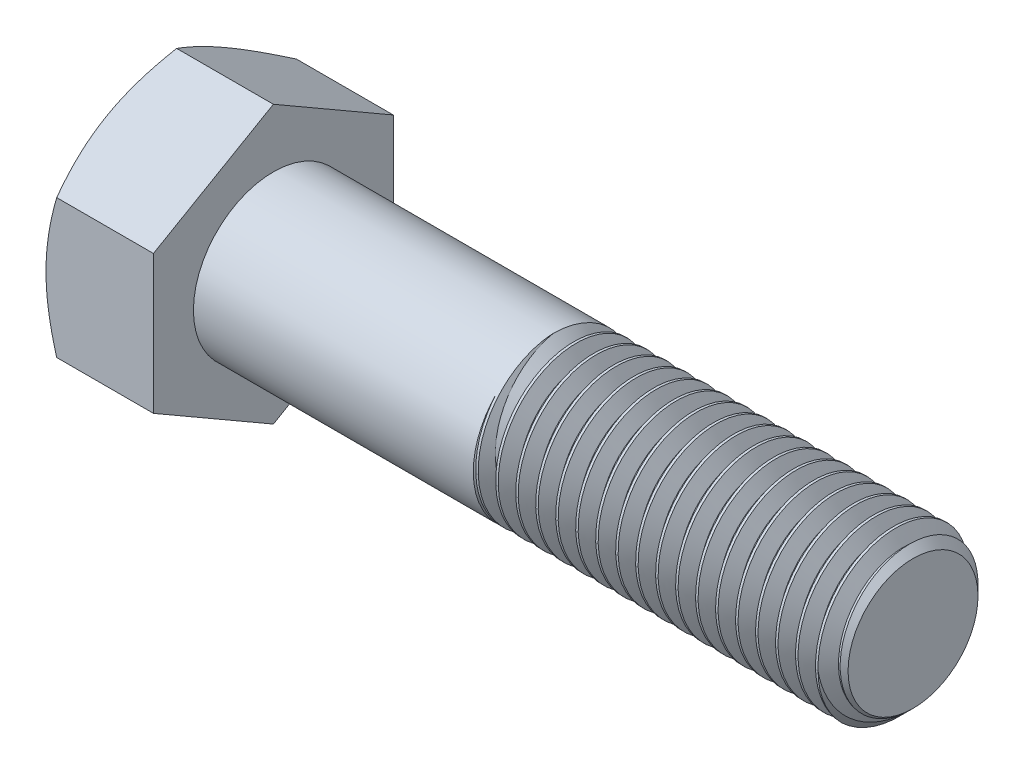
SolidWorks part; units mm, degrees
material "Alloy Steel"
ref_plane "Front Plane" through (0, 0, 0) normal (0, 0, 1) x (1, 0, 0)
ref_plane "Top Plane" through (0, 0, 0) normal (0, 1, 0) x (1, 0, 0)
ref_plane "Right Plane" through (0, 0, 0) normal (1, 0, 0) x (0, 0, -1)
sketch "Sketch1" plane through (0, 0, 0) normal (0, 0, 1) x (1, 0, 0)
  line L0 (-59.3328, 0) -> (59.3328, 0) construction
  line L1 (59.3328, 12.7) -> (59.3328, -12.7) construction
  line L2 (-42.2672, 19.05) -> (-42.2672, -19.05) construction
  line L3 (-59.3328, 19.05) -> (-59.3328, -19.05) construction
  point P9 (-42.2672, 0)
  point P10 (48.2203, -12.7)
  dimension "Screw Dia" = 25.4
  dimension "Hex" = 38.1
  dimension "Head Ht" = 17.0656
  dimension "Screw Lenght" = 101.6
  dimension "D1" = 11.1125
ref_plane "Plane2" through (59.3328, 0, 0) normal (1, 0, 0) x (0, 0, -1)
sketch "Sketch5" plane through (59.3328, 0, 0) normal (1, 0, 0) x (0, 0, -1)
  circle A0 centre (0, 0) radius 12.7
extrude "Boss-Extrude3" add sketch "Sketch5" against normal up to vertex (101.6 mm away) up to point (-42.2672, 0, 0)
sketch "Sketch9" plane through (59.3328, 0, 0) normal (1, 0, 0) x (0, 0, -1)
  circle A1 centre (0, 0) radius 12.7
  circle A2 centre (0, 0) radius 12.7
  dimension "D1" = 0
curve "Helix/Spiral1" pitch 3.175 height 60.325 turns 19 parameters "Pitch"=3.175
chamfer "Chamfer1" distance 2.3813 angle 45 1 edges at (59.3328, 0, -12.7)
sketch "Sketch10" plane through (0, 0, 0) normal (0, 0, 1) x (1, 0, 0)
  line L0 (59.3328, 12.7) -> (60.5234, 10.6378)
  line L1 (60.5234, 10.6378) -> (60.9203, 10.6378)
  line L2 (60.9203, 10.6378) -> (62.1109, 12.7)
  line L3 (59.3328, 12.7) -> (62.1109, 12.7)
  line L4 (60.7219, 12.7) -> (60.7219, 10.6378) construction
  line L5 (59.9281, 11.6689) -> (61.5156, 11.6689) construction
  dimension "D1" = 60
  dimension "D2" = 0.3969
  dimension "D3" = 1.5875
sweep "Cut-Sweep1" cut profiles "Sketch10" path "Helix/Spiral1"
sketch "Sketch11" plane through (0, 0, 0) normal (0, 0, 1) x (1, 0, 0)
  line L0 (-42.2672, 12.7) -> (-42.2672, 0)
  line L1 (-42.2672, 0) -> (14.8828, 0)
  line L3 (14.8828, 0) -> (2.1828, 12.7)
  line L4 (-42.2672, 12.7) -> (2.1828, 12.7)
  dimension "D1" = 45
  dimension "MIn Thread" = 57.15
revolve "Revolve1" add sketch "Sketch11" angle 360 about L1
sketch "Sketch6" plane through (-42.2672, 0, 0) normal (-1, 0, 0) x (0, 0, 1)
  line L0 (0, 19.05) -> (0, -19.05) construction
  line L1 (19.05, 10.9985) -> (0, 21.997)
  line L2 (0, 21.997) -> (-19.05, 10.9985)
  line L3 (-19.05, 10.9985) -> (-19.05, -10.9985)
  line L4 (-19.05, -10.9985) -> (0, -21.997)
  line L5 (0, -21.997) -> (19.05, -10.9985)
  line L6 (19.05, -10.9985) -> (19.05, 10.9985)
  circle A0 centre (0, 0) radius 19.05 construction
extrude "Boss-Extrude4" add sketch "Sketch6" along normal up to vertex (17.0656 mm away) up to point (-59.3328, -19.05, 0)
sketch "Sketch7" plane through (-59.3328, 0, 0) normal (-1, 0, 0) x (0, 0, 1)
  circle A0 centre (0, 0) radius 19.05 construction
  circle A1 centre (0, 0) radius 19.05
sketch "Sketch8" plane through (-59.3328, 0, 0) normal (-1, 0, 0) x (0, 0, 1)
  circle A0 centre (0, 0) radius 19.05 construction
  circle A1 centre (0, 0) radius 19.05
extrude "Cut-Extrude3" cut sketch "Sketch8" against normal through all draft 60 flip side to cut
sketch "Sketch12" plane through (-59.3328, 0, 0) normal (-1, 0, 0) x (0, 0, 1)
  line L0 (0, 14.6685) -> (0, 8.1915) construction
  line L1 (0.5715, 14.6685) -> (0.5715, 8.1915)
  line L2 (-0.5715, 14.6685) -> (-0.5715, 8.1915)
  line L3 (0, 12.7) -> (0, -12.7) construction
  arc A0 (0.5715, 14.6685) -> (-0.5715, 14.6685) centre (0, 14.6685) ccw
  arc A1 (-0.5715, 8.1915) -> (0.5715, 8.1915) centre (0, 8.1915) ccw
  circle A3 centre (0, 0) radius 7.62 construction
  circle A4 centre (0, 0) radius 15.24 construction
  point P2 (0, 11.43)
  dimension "D1" = 15.24
  dimension "D3" = 30.48
  dimension "D2" = 1.143
extrude "Cut-Extrude4" cut sketch "Sketch12" against normal blind 0.254
pattern_circular "CirPattern1" count 3 over 360 about axis through (0, 0, 0) along (1, 0, 0) of "Cut-Extrude4"
equation "\"D2@Sketch10\" = \"Pitch@Helix/Spiral1\"*.125"
equation "\"D3@Sketch10\" = \"Pitch@Helix/Spiral1\"*.5"
equation "\"D3@Helix/Spiral1\" = \"MIn Thread@Sketch11\"+\"Pitch@Helix/Spiral1\""
equation "\"D1@Chamfer1\" = \"Pitch@Helix/Spiral1\"*.75"
equation "\"D1@Sketch12\" = \"Hex@Sketch1\"*.4"
equation "\"D3@Sketch12\" = \"Hex@Sketch1\"*.8"
equation "\"D2@Sketch12\" = \"Hex@Sketch1\"*.03"
equation "\"D1@Sketch1\" = \"Pitch@Helix/Spiral1\"*3.5"
